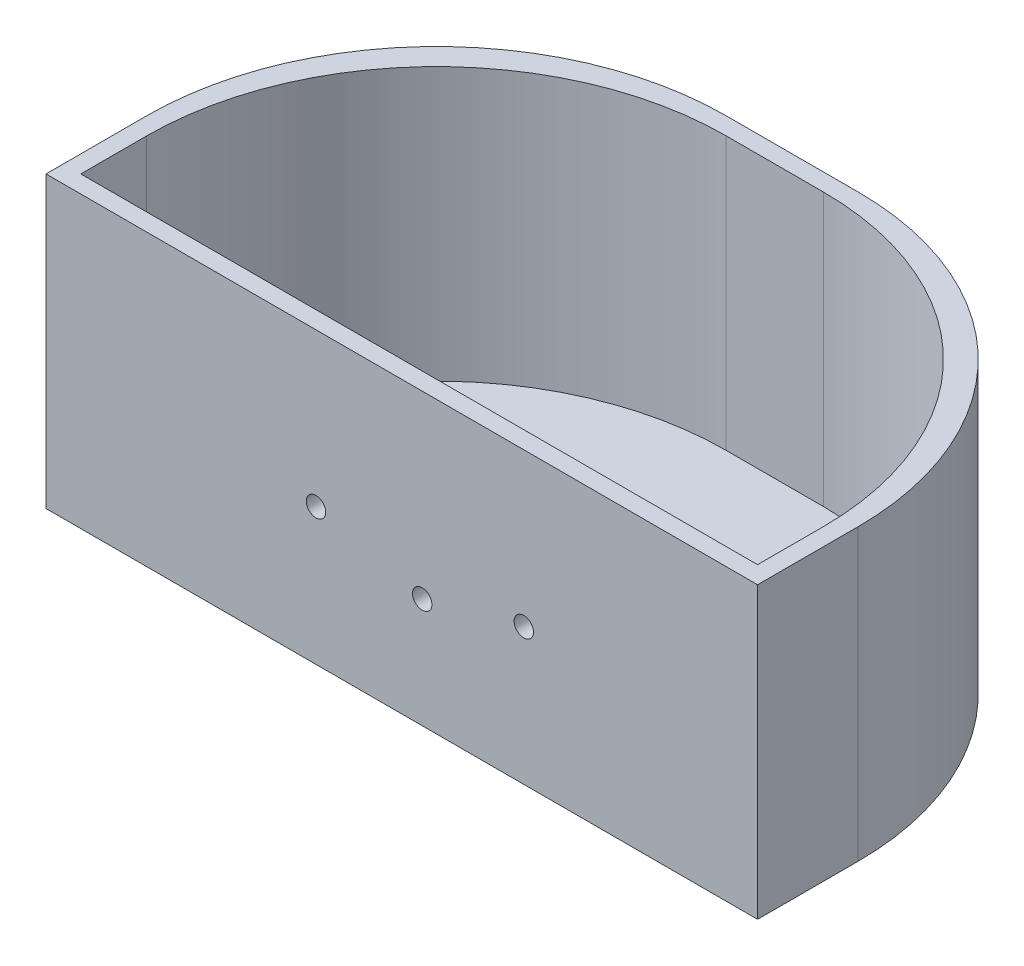
SolidWorks part; units mm, degrees
ref_plane "Front Plane" through (0, 0, 0) normal (0, 0, 1) x (1, 0, 0)
ref_plane "Top Plane" through (0, 0, 0) normal (0, 1, 0) x (1, 0, 0)
ref_plane "Right Plane" through (0, 0, 0) normal (1, 0, 0) x (0, 0, -1)
sketch "Sketch1" plane through (0, 0, 0) normal (0, 1, 0) x (1, 0, 0)
  line L1 (0, 0) -> (122.7714, 0)
  line L2 (0, 0) -> (0, 67.3648)
  line L3 (0, 67.3648) -> (122.7714, 67.3648)
  line L4 (122.7714, 0) -> (122.7714, 67.3648)
extrude "Boss-Extrude1" add sketch "Sketch1" along normal blind 50
sketch "Sketch2" plane through (0, 50, 0) normal (0, 1, 0) x (1, 0, 0)
  line L0 (0, 33.6824) -> (3, 33.6824) construction
  line L1 (0, 67.3648) -> (0, 0) construction
  line L2 (60.5151, 67.3648) -> (60.5151, 64.3648) construction
  line L3 (122.7714, 67.3648) -> (0, 67.3648) construction
  line L4 (122.7714, 33.6824) -> (119.7714, 33.6824) construction
  line L5 (122.7714, 0) -> (122.7714, 67.3648) construction
  line L6 (62.8973, 0) -> (62.8973, 3) construction
  line L7 (0, 0) -> (122.7714, 0) construction
  line L9 (3, 3) -> (119.7714, 3)
  line L10 (3, 3) -> (3, 64.3648)
  line L11 (3, 64.3648) -> (119.7714, 64.3648)
  line L12 (119.7714, 3) -> (119.7714, 64.3648)
extrude "Cut-Extrude1" cut sketch "Sketch2" against normal offset from surface (47 mm away) 3 up to face at (61.3857, 0, -33.6824)
sketch "Sketch3" plane through (0, 0, 0) normal (0, 0, 1) x (1, 0, 0)
  circle A0 centre (46.5832, 23.57) radius 1.6769
  circle A1 centre (64.9128, 18.9429) radius 1.6769
  circle A2 centre (82.4398, 23.57) radius 1.6769
  point P4 (65.1728, 23.57)
  point P7 (82.4398, 23.57)
  point P8 (64.9128, 18.9429)
extrude "Cut-Extrude3" cut sketch "Sketch3" against normal up to surface (3 mm away) up to face at (61.3857, 26.5, -3)
fillet "Fillet7" radius 50 1 edges at (119.7714, 26.5, -64.3648) type face fillet first side face at (61.3857, 26.5, -64.3648) second side face at (119.7714, 26.5, -33.6824)
fillet "Fillet8" radius 50 1 edges at (122.7714, 25, -67.3648) type face fillet first side face at (61.3857, 25, -67.3648) second side face at (122.7714, 25, -33.6824)
fillet "Fillet9" radius 50 1 edges at (3, 26.5, -64.3648) type face fillet first side face at (36.3857, 26.5, -64.3648) second side face at (3, 26.5, -33.6824)
fillet "Fillet10" radius 50 1 edges at (0, 25, -67.3648) type face fillet first side face at (36.3857, 25, -67.3648) second side face at (0, 25, -33.6824)
